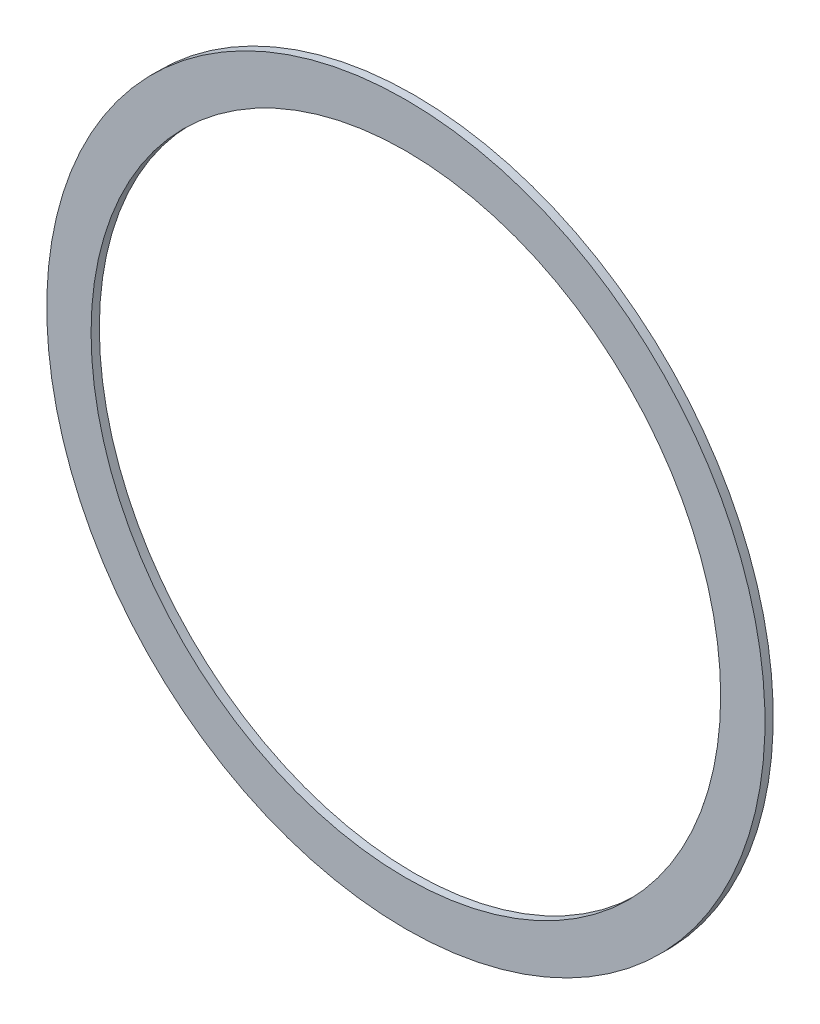
SolidWorks part; units mm, degrees
material "Balsa"
ref_plane "Front Plane" through (0, 0, 0) normal (0, 0, 1) x (1, 0, 0)
ref_plane "Top Plane" through (0, 0, 0) normal (0, 1, 0) x (1, 0, 0)
ref_plane "Right Plane" through (0, 0, 0) normal (1, 0, 0) x (0, 0, -1)
sketch "Sketch1" plane through (0, 0, 0) normal (0, 0, 1) x (1, 0, 0)
  line L0 (0, 0) -> (0, 499.9473) construction
  line L1 (0, -114.7984) -> (0, -129.4545) construction
  line L2 (0, -374.4718) -> (0, 404.2655) construction
  line L3 (-1.651, 142.9921) -> (-1.651, 150.6121) construction
  line L4 (1.651, 142.9921) -> (1.651, 150.6121) construction
  line L5 (-1.651, 142.9921) -> (1.651, 142.9921) construction
  line L6 (136.2041, -53.806) -> (0.0002, 24.7625) construction
  line L7 (-136.2076, -53.7991) -> (0.0002, 24.7625) construction
  line L8 (136.2041, -53.806) -> (0.0002, 24.7625) construction
  line L9 (-136.2076, -53.7991) -> (0.0002, 24.7625) construction
  line L10 (-125.0584, -45.4626) -> (-118.4576, -41.6554) construction
  line L11 (-123.6259, -48.4483) -> (-116.8078, -44.5157) construction
  line L12 (-118.4576, -41.6554) -> (-116.8078, -44.5157) construction
  line L13 (-124.1455, -48.7479) -> (-123.6847, -48.4822) construction
  line L14 (-123.6847, -48.4822) -> (-123.6259, -48.4483) construction
  line L15 (-125.7952, -45.8876) -> (-125.1113, -45.4931) construction
  line L16 (-125.1113, -45.4931) -> (-125.0584, -45.4626) construction
  line L17 (125.4797, -45.7137) -> (125.1075, -45.499) construction
  line L18 (123.8298, -48.5739) -> (123.6807, -48.488) construction
  line L19 (117.0223, -44.647) -> (118.6722, -41.7868) construction
  line L20 (123.6807, -48.488) -> (123.6228, -48.4545) construction
  line L21 (123.6228, -48.4545) -> (117.0223, -44.647) construction
  line L22 (125.1075, -45.499) -> (125.0554, -45.4689) construction
  line L23 (125.0554, -45.4689) -> (118.6722, -41.7868) construction
  line L24 (-108.646, -44.1245) -> (-121.8597, -51.7592)
  line L25 (-107.0618, -46.8785) -> (-120.2754, -54.5131)
  line L26 (-107.0618, -46.8785) -> (-120.2754, -54.5131) construction
  line L27 (-108.646, -44.1245) -> (-121.8597, -51.7592) construction
  line L28 (-115.4206, -47.9666) -> (-121.9445, -51.7361) construction
  line L29 (-120.2754, -54.5131) -> (-108.646, -44.1245) construction
  line L30 (-114.4607, -49.3188) -> (-122.1124, -53.7399) construction
  line L31 (-113.7686, -50.8257) -> (-120.3665, -54.6379) construction
  line L32 (-115.4206, -47.9666) -> (-113.7686, -50.8257) construction
  line L33 (107.3025, -47.0245) -> (129.9098, -60.0883)
  line L34 (108.8884, -44.2715) -> (131.505, -57.3407)
  line L35 (129.9098, -60.0883) -> (131.505, -57.3407)
  line L36 (129.9098, -60.0883) -> (131.505, -57.3407) construction
  line L37 (108.8884, -44.2715) -> (131.505, -57.3407) construction
  line L38 (107.3025, -47.0245) -> (129.9098, -60.0883) construction
  line L39 (129.9098, -60.0883) -> (108.8884, -44.2715) construction
  line L40 (119.3991, -52.1799) -> (101.8722, -42.0519) construction
  line L41 (120.3631, -54.6438) -> (113.7655, -50.8313)
  line L42 (122.0152, -51.7848) -> (122.0057, -51.7794) construction
  line L43 (113.7655, -50.8313) -> (115.4176, -47.9723)
  line L44 (122.0057, -51.7794) -> (121.9413, -51.7421) construction
  line L45 (121.9413, -51.7421) -> (115.4176, -47.9723)
  arc A0 (-1.651, 150.6121) -> (-125.0584, -45.4626) centre (0, 12.7) ccw
  circle A1 centre (0, 12.7) radius 120.904
  arc A2 (0, 150.622) -> (-1.651, 150.6121) centre (0, 12.7) ccw
  circle A3 centre (0, 12.7) radius 137.922 construction
  arc A4 (1.651, 150.6121) -> (0, 150.622) centre (0, 12.7) ccw
  arc A5 (-124.3508, -46.9604) -> (-123.6259, -48.4483) centre (0, 12.7) ccw
  arc A6 (-123.6259, -48.4483) -> (-121.9445, -51.7361) centre (0, 12.7) ccw
  arc A7 (-125.0584, -45.4626) -> (-124.3508, -46.9604) centre (0, 12.7) ccw
  arc A8 (124.3477, -46.9667) -> (125.0554, -45.4689) centre (0, 12.7) ccw
  arc A9 (125.0554, -45.4689) -> (1.651, 150.6121) centre (0, 12.7) ccw
  arc A10 (123.6228, -48.4545) -> (124.3477, -46.9667) centre (0, 12.7) ccw
  arc A11 (-121.9153, -51.7914) -> (-121.1641, -53.1919) centre (0, 12.7) ccw
  arc A12 (-120.3665, -54.6379) -> (120.3631, -54.6438) centre (0, 12.7) ccw
  arc A13 (-121.9445, -51.7361) -> (-121.9153, -51.7914) centre (0, 12.7) ccw
  arc A14 (-121.1641, -53.1919) -> (-120.3827, -54.6089) centre (0, 12.7) ccw
  arc A15 (-120.3827, -54.6089) -> (-120.397, -54.5834) centre (0, 12.7) ccw construction
  arc A16 (-120.397, -54.5834) -> (-120.3665, -54.6379) centre (0, 12.7) ccw construction
  arc A17 (120.3936, -54.5893) -> (121.0419, -53.416) centre (0, 12.7) ccw construction
  arc A18 (121.9413, -51.7421) -> (123.6228, -48.4545) centre (0, 12.7) ccw
  arc A19 (120.3631, -54.6438) -> (120.3936, -54.5893) centre (0, 12.7) ccw construction
  arc A20 (121.0419, -53.416) -> (121.9121, -51.7974) centre (0, 12.7) ccw construction
  arc A21 (121.9121, -51.7974) -> (121.9413, -51.7421) centre (0, 12.7) ccw construction
  spline S0 degree 3 poles (-891.8479, -1778.6566) (-223.5651, -622.3771) (442.5776, 534.0478) (1105.5233, 1688.7852) knots -629.037343 -629.037343 -629.037343 -629.037343 630.975162 630.975162 630.975162 630.975162 weights 1.000396 0.999868 0.999868 1.000397 only from (107.3025, -47.0245) to (108.8884, -44.2715)
  spline S1 degree 3 poles (-66.0123, 133.6164) (-70.0128, 131.4329) (-73.8716, 129.0699) (-81.3156, 123.9975) (-84.9009, 121.288) (-91.7995, 115.5249) (-95.113, 112.4712) (-99.0811, 108.4341) (-99.866, 107.6157) (-101.4182, 105.9565) (-102.1865, 105.1147) (-104.4569, 102.5643) (-105.9223, 100.8334) (-110.1768, 95.5512) (-115.4725, 88.2691) (-120.0285, 80.5179) (-123.1654, 74.5269) (-124.1643, 72.5002) (-125.5914, 69.415) (-126.0551, 68.3791) (-126.9587, 66.292) (-127.3989, 65.2397) (-129.5278, 59.9684) (-131.0098, 55.7) (-133.5456, 47.0638) (-134.5993, 42.696) (-136.2795, 33.8613) (-136.906, 29.3944) (-137.415, 23.7472) (-137.5031, 22.6146) (-137.6514, 20.3429) (-137.7116, 19.2049) (-137.8496, 15.7999) (-137.8852, 13.5361) (-137.8263, 6.7629) (-137.3062, -2.2197) (-135.9163, -11.1068) (-134.5433, -17.7359) (-134.0304, -19.9395) (-132.8922, -24.3345) (-132.2653, -26.5303) (-130.2347, -33.03) (-128.6774, -37.2656) (-126.1245, -43.2881) (-125.286, -45.1501) (-124.4066, -46.9926) knots 0 0 0 0 0.03125 0.03125 0.0625 0.0625 0.09375 0.09375 0.101563 0.101563 0.109375 0.109375 0.125 0.125 0.15625 0.1875 0.1875 0.203125 0.203125 0.210938 0.210938 0.21875 0.21875 0.25 0.25 0.28125 0.28125 0.3125 0.3125 0.320313 0.320313 0.328125 0.328125 0.34375 0.34375 0.375 0.40625 0.40625 0.421875 0.421875 0.4375 0.4375 0.46875 0.46875 0.48295 0.48295 0.48295 0.48295 construction
  spline S2 degree 3 poles (-1557.5256, 1030.3086) (-495.2142, -0.1753) (-82.1366, -210.7146) (81.4542, -98.9353) (85.033, -96.2237) (91.9188, -90.4573) (95.2258, -87.4025) (99.1858, -83.3647) (99.9691, -82.5461) (101.5182, -80.8868) (102.2849, -80.0449) (104.5506, -77.4941) (106.013, -75.7632) (110.2586, -70.4809) (112.9006, -66.8403) (117.8152, -59.3254) (120.0877, -55.4512) (123.2166, -49.4629) (124.2129, -47.4373) (125.6361, -44.3538) (126.0986, -43.3185) (126.9997, -41.2327) (127.4386, -40.181) (129.5618, -34.9121) (131.0396, -30.646) (133.5674, -22.0152) (134.6173, -17.6505) (136.2906, -8.8227) (136.914, -4.3596) (137.4197, 1.2823) (137.5071, 2.4139) (137.6542, 4.6834) (137.7138, 5.8206) (137.85, 9.2232) (137.8846, 11.4853) (137.8228, 18.2533) (137.2995, 27.2283) (135.9081, 36.1069) (134.5347, 42.7292) (134.0218, 44.9305) (132.8839, 49.3207) (132.2571, 51.5145) (130.2267, 58.0093) (128.67, 62.2416) (125.1615, 70.5162) (123.2097, 74.5586) (118.9108, 82.4534) (116.5637, 86.3058) (113.3753, 90.999) (112.7241, 91.9325) (111.3996, 93.7822) (110.7272, 94.697) (108.6802, 97.4113) (107.2757, 99.181) (102.9447, 104.3725) (96.8571, 110.9816) (90.1513, 116.9722) (84.8861, 121.2292) (83.0917, 122.6088) (80.3399, 124.6181) (79.4113, 125.2786) (77.543, 126.5731) (76.6028, 127.2075) (71.8708, 130.3161) (67.9881, 132.6004) (60.0328, 136.7739) (55.9603, 138.6631) (47.6249, 142.0446) (43.3619, 143.537) (37.9102, 145.1462) (36.8136, 145.4551) (34.6205, 146.0438) (33.5224, 146.3241) (30.2234, 147.1229) (28.0179, 147.5997) (21.3832, 148.8649) (16.9358, 149.4889) (7.993, 150.3014) (3.4975, 150.4899) (-3.2824, 150.4396) (-5.5486, 150.3672) (-10.0934, 150.1088) (-12.3559, 149.9236) (-19.101, 149.2046) (-23.5473, 148.5072) (-32.3412, 146.6856) (-36.6887, 145.5614) (-43.1354, 143.5526) (-45.2718, 142.8291) (-49.5193, 141.273) (-51.6323, 140.4395) (-274.1905, 46.1884) (-224.836, -608.7963) (101.1574, -1839.6029) knots -1.31339 -1.31339 -1.31339 -1.31339 0.03125 0.03125 0.0625 0.0625 0.09375 0.09375 0.101563 0.101563 0.109375 0.109375 0.125 0.125 0.15625 0.15625 0.1875 0.1875 0.203125 0.203125 0.210938 0.210938 0.21875 0.21875 0.25 0.25 0.28125 0.28125 0.3125 0.3125 0.320313 0.320313 0.328125 0.328125 0.34375 0.34375 0.375 0.40625 0.40625 0.421875 0.421875 0.4375 0.4375 0.46875 0.46875 0.5 0.5 0.53125 0.53125 0.539062 0.539062 0.546875 0.546875 0.5625 0.5625 0.59375 0.625 0.625 0.640625 0.640625 0.648437 0.648437 0.65625 0.65625 0.6875 0.6875 0.71875 0.71875 0.75 0.75 0.757812 0.757812 0.765625 0.765625 0.78125 0.78125 0.8125 0.8125 0.84375 0.84375 0.859375 0.859375 0.875 0.875 0.90625 0.90625 0.9375 0.9375 0.953125 0.953125 0.96875 0.96875 2.612134 2.612134 2.612134 2.612134 only from (66.1767, -108.566) to (-66.0123, 133.6164)
  spline S3 degree 3 poles (66.1767, -108.566) (70.1708, -106.3789) (74.0231, -104.0129) (81.4542, -98.9353) (85.033, -96.2237) (91.9188, -90.4573) (95.2258, -87.4025) (99.1858, -83.3647) (99.9691, -82.5461) (101.5182, -80.8868) (102.2849, -80.0449) (104.5506, -77.4941) (106.013, -75.7632) (110.2586, -70.4809) (112.9006, -66.8403) (117.8152, -59.3254) (120.0877, -55.4512) (123.2166, -49.4629) (124.2129, -47.4373) (125.6361, -44.3538) (126.0986, -43.3185) (126.9997, -41.2327) (127.4386, -40.181) (129.5618, -34.9121) (131.0396, -30.646) (133.5674, -22.0152) (134.6173, -17.6505) (136.2906, -8.8227) (136.914, -4.3596) (137.4197, 1.2823) (137.5071, 2.4139) (137.6542, 4.6834) (137.7138, 5.8206) (137.85, 9.2232) (137.8846, 11.4853) (137.8228, 18.2533) (137.2995, 27.2283) (135.9081, 36.1069) (134.5347, 42.7292) (134.0218, 44.9305) (132.8839, 49.3207) (132.2571, 51.5145) (130.2267, 58.0093) (128.67, 62.2416) (125.1615, 70.5162) (123.2097, 74.5586) (118.9108, 82.4534) (116.5637, 86.3058) (113.3753, 90.999) (112.7241, 91.9325) (111.3996, 93.7822) (110.7272, 94.697) (108.6802, 97.4113) (107.2757, 99.181) (102.9447, 104.3725) (96.8571, 110.9816) (90.1513, 116.9722) (84.8861, 121.2292) (83.0917, 122.6088) (80.3399, 124.6181) (79.4113, 125.2786) (77.543, 126.5731) (76.6028, 127.2075) (71.8708, 130.3161) (67.9881, 132.6004) (60.0328, 136.7739) (55.9603, 138.6631) (47.6249, 142.0446) (43.3619, 143.537) (37.9102, 145.1462) (36.8136, 145.4551) (34.6205, 146.0438) (33.5224, 146.3241) (30.2234, 147.1229) (28.0179, 147.5997) (21.3832, 148.8649) (16.9358, 149.4889) (7.993, 150.3014) (3.4975, 150.4899) (-3.2824, 150.4396) (-5.5486, 150.3672) (-10.0934, 150.1088) (-12.3559, 149.9236) (-19.101, 149.2046) (-23.5473, 148.5072) (-32.3412, 146.6856) (-36.6887, 145.5614) (-43.1354, 143.5526) (-45.2718, 142.8291) (-49.5193, 141.273) (-51.6323, 140.4395) (-57.9206, 137.7764) (-62.0153, 135.798) (-66.0123, 133.6164) knots 0 0 0 0 0.03125 0.03125 0.0625 0.0625 0.09375 0.09375 0.101563 0.101563 0.109375 0.109375 0.125 0.125 0.15625 0.15625 0.1875 0.1875 0.203125 0.203125 0.210938 0.210938 0.21875 0.21875 0.25 0.25 0.28125 0.28125 0.3125 0.3125 0.320313 0.320313 0.328125 0.328125 0.34375 0.34375 0.375 0.40625 0.40625 0.421875 0.421875 0.4375 0.4375 0.46875 0.46875 0.5 0.5 0.53125 0.53125 0.539062 0.539062 0.546875 0.546875 0.5625 0.5625 0.59375 0.625 0.625 0.640625 0.640625 0.648437 0.648437 0.65625 0.65625 0.6875 0.6875 0.71875 0.71875 0.75 0.75 0.757812 0.757812 0.765625 0.765625 0.78125 0.78125 0.8125 0.8125 0.84375 0.84375 0.859375 0.859375 0.875 0.875 0.90625 0.90625 0.9375 0.9375 0.953125 0.953125 0.96875 0.96875 1 1 1 1 construction
  spline S4 degree 3 poles (-124.4066, -46.9926) (-124.169, -47.4906) (-123.9283, -47.9871) (-123.6847, -48.4822) knots 0.48295 0.48295 0.48295 0.48295 0.486788 0.486788 0.486788 0.486788 construction
  spline S5 degree 3 poles (-123.6847, -48.4822) (-122.846, -50.1865) (-121.9718, -51.874) (-118.9108, -57.4955) (-116.5612, -61.3517) (-113.369, -66.0497) (-112.7169, -66.9844) (-111.3913, -68.8351) (-110.7184, -69.7503) (-108.6697, -72.4662) (-107.264, -74.2369) (-102.929, -79.4315) (-96.8353, -86.0447) (-90.1214, -92.0392) (-84.8493, -96.299) (-83.0524, -97.6795) (-80.2967, -99.6899) (-79.367, -100.3507) (-77.4971, -101.6451) (-76.5559, -102.2795) (-71.8198, -105.3881) (-67.9332, -107.6723) (-59.9695, -111.8452) (-55.8924, -113.7339) (-47.5468, -117.114) (-43.2782, -118.6053) (-37.8188, -120.2127) (-36.7216, -120.521) (-34.5268, -121.1085) (-33.4279, -121.3881) (-30.1264, -122.185) (-27.9191, -122.6605) (-21.2788, -123.9216) (-16.8274, -124.5426) (-7.8757, -125.3484) (-3.3755, -125.5332) (3.4122, -125.4766) (5.6812, -125.4019) (10.231, -125.1387) (12.493, -124.9512) (19.2413, -124.2249) (23.6899, -123.5224) (32.4889, -121.6898) (36.8393, -120.5597) (43.2904, -118.5412) (45.4283, -117.8143) (48.6163, -116.6419) (49.6759, -116.2374) (51.7885, -115.4006) (52.8426, -114.968) (58.0839, -112.7404) (62.1792, -110.755) (66.1767, -108.566) knots 0.486788 0.486788 0.486788 0.486788 0.5 0.5 0.53125 0.53125 0.539062 0.539062 0.546875 0.546875 0.5625 0.5625 0.59375 0.625 0.625 0.640625 0.640625 0.648437 0.648437 0.65625 0.65625 0.6875 0.6875 0.71875 0.71875 0.75 0.75 0.757812 0.757812 0.765625 0.765625 0.78125 0.78125 0.8125 0.8125 0.84375 0.84375 0.859375 0.859375 0.875 0.875 0.90625 0.90625 0.9375 0.9375 0.953125 0.953125 0.960937 0.960937 0.96875 0.96875 1 1 1 1 construction
  spline S6 degree 3 poles (-2106.0776, 3411.0958) (-795.1269, 1114.0106) (536.0971, -1200.0631) (1875.8435, -3510.6923) knots -1262.072517 -1262.072517 -1262.072517 -1262.072517 1256.953485 1256.953485 1256.953485 1256.953485 weights 1.002223 0.999266 0.999259 1.002202 only from (-121.8597, -51.7592) to (-120.2754, -54.5131)
  spline S7 degree 3 poles (-121.0676, -53.1362) (-120.8035, -53.5952) (-120.5395, -54.0542) (-120.2754, -54.5131) knots 0.5 0.5 0.5 0.5 1 1 1 1 weights 1 1 1 1 construction
  spline S8 degree 3 poles (-1103.85, 1689.3566) (-442.753, 535.5166) (222.748, -621.3602) (891.1502, -1778.662) knots -630.285082 -630.285082 -630.285082 -630.285082 629.725462 629.725462 629.725462 629.725462 weights 1.000566 0.999812 0.999811 1.000563 only from (-108.646, -44.1245) to (-107.0618, -46.8785)
  spline S9 degree 3 poles (-121.8597, -51.7592) (-121.5957, -52.2182) (-121.3316, -52.6772) (-121.0676, -53.1362) knots 0 0 0 0 0.5 0.5 0.5 0.5 weights 1 1 1 1 construction
  spline S10 degree 3 poles (-108.646, -44.1245) (-108.118, -45.0425) (-107.5899, -45.9605) (-107.0618, -46.8785) knots 0 0 0 0 1 1 1 1 weights 1 1 1 1
  spline S11 degree 3 poles (107.3025, -47.0245) (107.8311, -46.1069) (108.3597, -45.1892) (108.8884, -44.2715) knots 0 0 0 0 1 1 1 1 weights 1 1 1 1
  point P7 (0, -125.5003)
  point P8 (0, 150.4602)
  point P25 (-125.0584, -45.4626)
  point P38 (123.6228, -48.4545)
  dimension "D2" = 275.844
  dimension "D1" = 275.9605
  dimension "D3" = 12.7
  dimension "D5" = 3.302
  dimension "D6" = 7.62
  dimension "D7" = 3.302
  dimension "D8" = 7.62
  dimension "D9" = 3.302
  dimension "D10" = 7.62
  dimension "D11" = 3.302
  dimension "D12" = 7.62
  dimension "D13" = 3.302
  dimension "D14" = 7.62
  dimension "D4" = 17.018
extrude "Boss-Extrude1" [suppressed] add sketch "Sketch1" along normal mid plane 3.175
sketch "Sketch2" plane through (248.2736, -245.0135, 0) normal (0, 0, -1) x (0, -1, 0)
  line L3 (-245.0135, 248.2736) -> (-427.6569, 248.2736) construction
  circle A1 centre (-257.7135, 248.2736) radius 137.922
  circle A16 centre (-257.7135, 248.2736) radius 120.904
  dimension "D1" = 12.7
  dimension "D2" = 275.844
  dimension "D3" = 17.018
fillet "Fillet1" [suppressed] radius 1.27
extrude "Boss-Extrude2" add sketch "Sketch2" along normal mid plane 3.175
equation "\"slotwidth\"=0.13"
equation "\"D11@Sketch1\"=\"slotwidth\""
